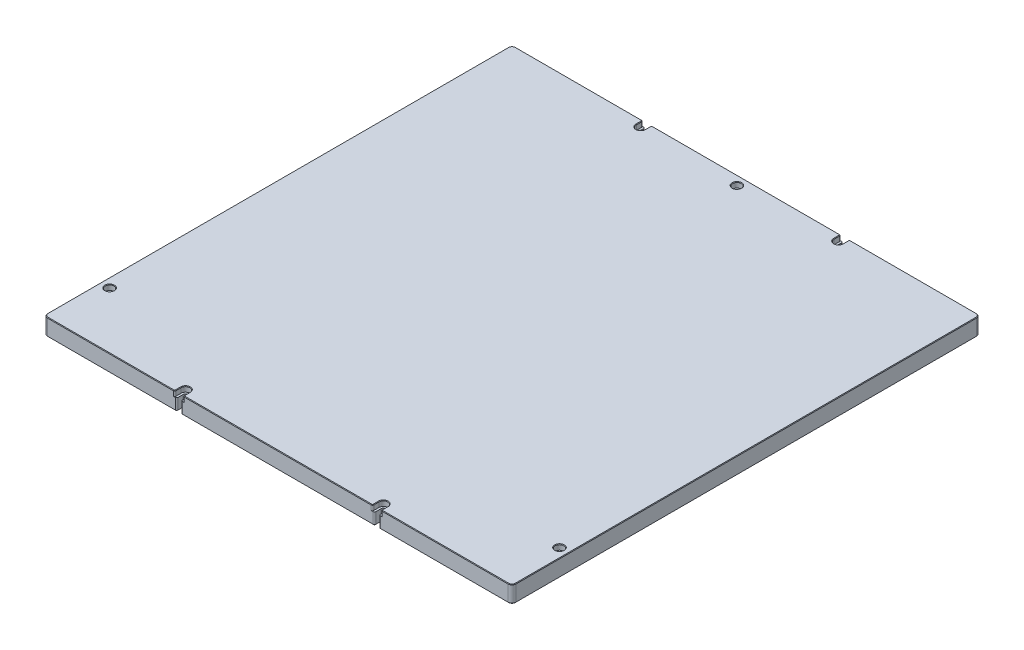
SolidWorks part; units mm, degrees
note: The reader was unsure of these and kept them because the rebuilt part matched: shared geometry of "Sketch4<3>".
ref_plane "Front Plane" through (0, 0, 0) normal (0, 0, 1) x (1, 0, 0)
ref_plane "Top Plane" through (0, 0, 0) normal (0, 1, 0) x (1, 0, 0)
ref_plane "Right Plane" through (0, 0, 0) normal (1, 0, 0) x (0, 0, -1)
sketch "Sketch1" plane through (0, 0, 0) normal (0, 1, 0) x (1, 0, 0)
  line L1 (-177.5, 177.5) -> (177.5, 177.5)
  line L2 (-177.5, 177.5) -> (-177.5, -177.5)
  line L3 (-177.5, -177.5) -> (177.5, -177.5)
  line L4 (177.5, 177.5) -> (177.5, -177.5)
  line L5 (-177.5, 177.5) -> (177.5, -177.5) construction
  line L6 (-177.5, -177.5) -> (177.5, 177.5) construction
  point P0 (0, 0)
  dimension "D1" = 355
extrude "Boss-Extrude1" add sketch "Sketch1" against normal blind 12.7
sketch "Sketch2" plane through (0, 0, 0) normal (0, 1, 0) x (1, 0, 0)
  line L0 (177.5, -177.5) -> (177.5, 177.5) construction
  line L1 (-177.5, 177.5) -> (-177.5, -177.5) construction
  line L2 (177.5, 177.5) -> (-177.5, 177.5) construction
  point P0 (-170.5, -134.5)
  point P1 (170.5, -134.5)
  point P2 (0, 170.5)
  dimension "D1" = 7
  dimension "D2" = 7
  dimension "D3" = 305
  dimension "D4" = 7
hole_wizard "CBORE for M3 Hex Socket Head Cap Screw1" positions "Sketch2" profile "Sketch3" counterbore size "M3" standard "DIN" end condition through all
sketch "Sketch3" plane through (-170.5, 0, 134.5) normal (1, 0, 0) x (0, 0, 1)
  line L0 (0, 0) -> (0, 12.7)
  line L1 (0, 12.7) -> (1.7, 12.7)
  line L3 (1.7, 12.7) -> (1.7, 4)
  line L4 (1.7, 4) -> (3.25, 4)
  line L5 (3.25, 4) -> (3.25, 0)
  line L7 (3.25, 0) -> (0, 0)
  line L11 (0, -6.35) -> (0, 107.95) construction
  dimension "Thru Hole Dia." = 3.4
  dimension "Thru Hole Depth" = 12.7
  dimension "C'Bore Dia." = 6.5
  dimension "C'Bore Depth" = 4
sketch "Sketch4" plane through (0, 0, 0) normal (0, 1, 0) x (1, 0, 0)
  line L0 (-76.7, -177.5) -> (-76.7, -172.5)
  line L1 (-177.5, -177.5) -> (177.5, -177.5) construction
  line L2 (-73.3, -172.5) -> (-73.3, -177.5)
  line L3 (73.3, -177.5) -> (73.3, -172.5)
  line L4 (76.7, -172.5) -> (76.7, -177.5)
  line L5 (-76.7, 177.5) -> (-76.7, 172.5)
  line L6 (177.5, 177.5) -> (-177.5, 177.5) construction
  line L7 (-73.3, 172.5) -> (-73.3, 177.5)
  line L8 (73.3, 177.5) -> (73.3, 172.5)
  line L9 (76.7, 172.5) -> (76.7, 177.5)
  line L10 (-76.7, 177.5) -> (-73.3, 177.5)
  line L11 (73.3, 177.5) -> (76.7, 177.5)
  line L12 (76.7, -177.5) -> (73.3, -177.5)
  line L13 (-73.3, -177.5) -> (-76.7, -177.5)
  line L14 (-75, -172.5) -> (75, -172.5) construction
  line L15 (-78.25, -179.05) -> (-78.25, -172.5)
  line L16 (-71.75, -172.5) -> (-71.75, -179.05)
  line L17 (-71.75, -179.05) -> (-78.25, -179.05)
  line L18 (71.75, -179.05) -> (71.75, -172.5)
  line L19 (78.25, -172.5) -> (78.25, -179.05)
  line L20 (78.25, -179.05) -> (71.75, -179.05)
  line L21 (71.75, 179.05) -> (71.75, 172.5)
  line L22 (78.25, 172.5) -> (78.25, 179.05)
  line L23 (71.75, 179.05) -> (78.25, 179.05)
  line L24 (-71.75, 172.5) -> (-71.75, 179.05)
  line L25 (-78.25, 179.05) -> (-71.75, 179.05)
  line L26 (-78.25, 179.05) -> (-78.25, 172.5)
  arc A0 (-76.7, -172.5) -> (-73.3, -172.5) centre (-75, -172.5) cw
  arc A1 (73.3, -172.5) -> (76.7, -172.5) centre (75, -172.5) cw
  arc A2 (-76.7, 172.5) -> (-73.3, 172.5) centre (-75, 172.5) ccw
  arc A3 (73.3, 172.5) -> (76.7, 172.5) centre (75, 172.5) ccw
  arc A4 (-78.25, -172.5) -> (-71.75, -172.5) centre (-75, -172.5) cw
  arc A5 (71.75, -172.5) -> (78.25, -172.5) centre (75, -172.5) cw
  arc A6 (71.75, 172.5) -> (78.25, 172.5) centre (75, 172.5) ccw
  arc A7 (-78.25, 172.5) -> (-71.75, 172.5) centre (-75, 172.5) ccw
  point P23 (0, -172.5)
  dimension "D1" = 3.4
  dimension "D2" = 5
  dimension "D3" = 150
  dimension "D4" = 1.55
extrude "Cut-Extrude1" cut sketch "Sketch4" against normal through all
extrude "Cut-Extrude2" cut sketch "Sketch4<3>" against normal blind 4
sketch "Sketch4<3>" plane through (0, 0, 0) normal (0, 1, 0) x (1, 0, 0) same geometry as "Sketch4"
fillet "Fillet2" radius 1 16 edges at (-71.75, -2, 177.5) (-73.3, -8.35, 177.5) (-76.7, -8.35, 177.5) (-78.25, -2, 177.5) (-73.3, -8.35, -177.5) (-76.7, -8.35, -177.5) (-78.25, -2, -177.5) (-71.75, -2, -177.5) (71.75, -2, -177.5) (73.3, -8.35, -177.5) (76.7, -8.35, -177.5) (78.25, -2, -177.5) (76.7, -8.35, 177.5) (78.25, -2, 177.5) (73.3, -8.35, 177.5) (71.75, -2, 177.5)
sketch "Sketch5" plane through (0, -12.7, 0) normal (0, -1, 0) x (1, 0, 0)
  line L0 (-37.5, -170.5) -> (37.5, -170.5) construction
  circle A0 centre (-37.5, -170.5) radius 1.7
  circle A1 centre (37.5, -170.5) radius 1.7
  circle A2 centre (0, -170.5) radius 1.7 construction
  circle A3 centre (0, -170.5) radius 1.7
  point P8 (0, -170.5)
  dimension "D2" = 3.4
  dimension "D1" = 37.5
extrude "Cut-Extrude3" cut sketch "Sketch5" against normal blind 6
fillet "Fillet1" radius 3 4 edges at (177.5, -6.35, -177.5) (-177.5, -6.35, -177.5) (177.5, -6.35, 177.5) (-177.5, -6.35, 177.5)
chamfer "Chamfer1" distance 0.4 angle 45 72 edges at (0, 0, -167.25) (170.5, 0, 137.75) (-170.5, 0, 137.75) (176.6213, 0, 176.6213) (126.875, 0, 177.5) (78.5429, 0, 177.2071) (78.25, 0, 174.5) (75, 0, 169.25) (71.75, 0, 174.5) (71.4571, 0, 177.2071) (0, 0, 177.5) (-71.4571, 0, 177.2071) (-71.75, 0, 174.5) (-75, 0, 169.25) (-78.25, 0, 174.5) (-78.5429, 0, 177.2071) (-126.875, 0, 177.5) (-176.6213, 0, 176.6213) (-177.5, 0, 0) (-176.6213, 0, -176.6213) (-126.875, 0, -177.5) (-78.5429, 0, -177.2071) (-78.25, 0, -174.5) (-75, 0, -169.25) (-71.75, 0, -174.5) (-71.4571, 0, -177.2071) (0, 0, -177.5) (71.4571, 0, -177.2071) (71.75, 0, -174.5) (75, 0, -169.25) (78.25, 0, -174.5) (78.5429, 0, -177.2071) (126.875, 0, -177.5) (176.6213, 0, -176.6213) (177.5, 0, 0) (76.9929, -12.7, -177.2071) (76.7, -12.7, -174.5) (75, -12.7, -170.8) (73.3, -12.7, -174.5) (73.0071, -12.7, -177.2071) (0, -12.7, -177.5) (-73.0071, -12.7, -177.2071) (-73.3, -12.7, -174.5) (-75, -12.7, -170.8) (-76.7, -12.7, -174.5) (-76.9929, -12.7, -177.2071) (-126.1, -12.7, -177.5) (-176.6213, -12.7, -176.6213) (-177.5, -12.7, 0) (-176.6213, -12.7, 176.6213) (-126.1, -12.7, 177.5) (-76.9929, -12.7, 177.2071) (-76.7, -12.7, 174.5) (-75, -12.7, 170.8) (-73.3, -12.7, 174.5) (-73.0071, -12.7, 177.2071) (0, -12.7, 177.5) (73.0071, -12.7, 177.2071) (73.3, -12.7, 174.5) (75, -12.7, 170.8) (76.7, -12.7, 174.5) (76.9929, -12.7, 177.2071) (126.1, -12.7, 177.5) (176.6213, -12.7, 176.6213) (177.5, -12.7, 0) (176.6213, -12.7, -176.6213) (126.1, -12.7, -177.5) (0, -12.7, -168.8) (170.5, -12.7, 136.2) (-170.5, -12.7, 136.2) (37.5, -12.7, -172.2) (-37.5, -12.7, -172.2)
equation "\"bed_thickness\"= 0.5in"
equation "\"D1@Boss-Extrude1\"=\"bed_thickness\""
